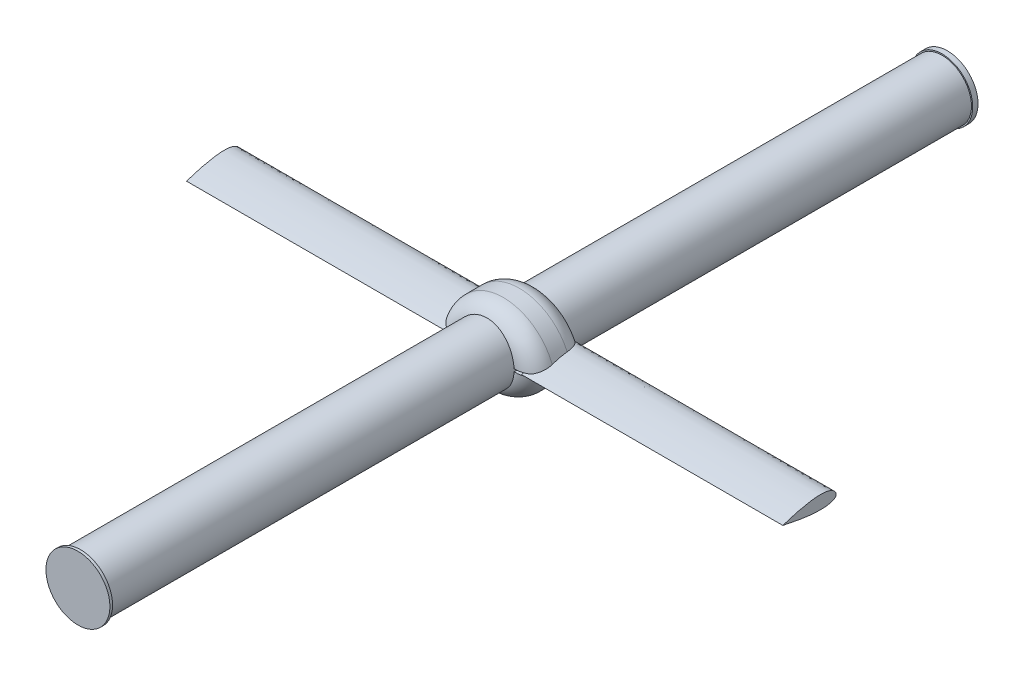
SolidWorks part; units mm, degrees
ref_plane "Front Plane" through (0, 0, 0) normal (0, 0, 1) x (1, 0, 0)
ref_plane "Top Plane" through (0, 0, 0) normal (0, 1, 0) x (1, 0, 0)
ref_plane "Right Plane" through (0, 0, 0) normal (1, 0, 0) x (0, 0, -1)
ref_plane "Plane1" through (0, 0, 10) normal (0, 0, 1) x (1, 0, 0)
sketch "Sketch1" plane through (0, 0, 10) normal (0, 0, 1) x (1, 0, 0)
  circle A0 centre (0, 0) radius 55.2
  dimension "D1" = 110.4
extrude "Boss-Extrude1" add sketch "Sketch1" along normal blind 798
sketch "Sketch3" plane through (0, 0, 808) normal (0, 0, 1) x (1, 0, 0)
  circle A0 centre (0, 0) radius 60
  dimension "D1" = 120
extrude "Boss-Extrude2" add sketch "Sketch3" along normal blind 5 contours A0
sketch "Sketch4" plane through (0, 0, 10) normal (0, 0, -1) x (-1, 0, 0)
  circle A0 centre (0, 0) radius 55.2
  dimension "D1" = 110.4
extrude "Boss-Extrude3" add sketch "Sketch4" along normal blind 20
sketch "Sketch5" plane through (0, 0, -10) normal (0, 0, -1) x (-1, 0, 0)
  circle A0 centre (0, 0) radius 55.2
  dimension "D1" = 110.4
extrude "Boss-Extrude4" add sketch "Sketch5" along normal blind 798
sketch "Sketch6" plane through (0, 0, -808) normal (0, 0, -1) x (-1, 0, 0)
  circle A0 centre (0, 0) radius 57.5
  dimension "D1" = 115
extrude "Boss-Extrude5" add sketch "Sketch6" along normal blind 10
sketch "Sketch10" plane through (0, 0, 0) normal (0, 0, 1) x (1, 0, 0)
  line L0 (-94.2708, 2.5) -> (-55.1434, 2.5)
  line L1 (55.1434, 2.5) -> (94.2708, 2.5)
  arc A0 (94.2708, 2.5) -> (-94.2708, 2.5) centre (0, -25) ccw
  arc A1 (55.1434, 2.5) -> (-55.1434, 2.5) centre (0, 0) ccw
  point P2 (0, 55.2)
  point P3 (0, -25)
  point P8 (0, 73.2)
  dimension "D1" = 55.2
  dimension "D2" = 18
  dimension "D3" = 0
  dimension "D4" = 25
  dimension "D5" = 2.5
extrude "Boss-Extrude8" add sketch "Sketch10" along normal mid plane 100
fillet "Fillet1" radius 35 1 edges at (0, 73.2, 50) type face fillet first side face at (0, 33.35, 50) second side face at (0, 37.85, 0)
fillet "Fillet2" radius 35 1 edges at (0, 73.2, -50) type face fillet first side face at (0, 33.35, -50) second side face at (0, 37.85, -17.5)
mirror "Mirror2" about plane through (0, 0, 0) normal (0, 1, 0) of "Fillet1", "Fillet2", "Boss-Extrude8"
ref_plane "Plane2" through (-94.2708, 0, 0) normal (-1, 0, 0) x (0, 0, 1)
ref_plane "Plane3" through (-69.2708, 0, 0) normal (-1, 0, 0) x (0, 0, 1)
sketch "Sketch11" plane through (-69.2708, 0, 0) normal (-1, 0, 0) x (0, 0, 1)
  spline S0 degree 4 poles (-50, 0) (-49.9991, 0.3297) (-49.9705, 0.9275) (-49.8561, 1.7967) (-49.563, 2.9181) (-49.1451, 3.9907) (-48.5685, 5.0756) (-47.8077, 6.1773) (-46.7997, 7.33) (-45.5041, 8.5106) (-43.846, 9.7149) (-41.7259, 10.9292) (-39.043, 12.1146) (-35.8523, 13.1525) (-31.9595, 14.0363) (-26.8657, 14.7366) (-20.7643, 15.0274) (-14.662, 14.8248) (-8.8989, 14.3138) (-3.159, 13.5968) (1.6037, 12.8505) (6.3456, 11.9834) (11.0671, 11.0139) (14.8328, 10.183) (18.5865, 9.3015) (22.3294, 8.3726) (26.0598, 7.3994) (29.3157, 6.5093) (32.096, 5.721) (34.4127, 5.0444) (36.2537, 4.4957) (38.1107, 3.9294) (39.9289, 3.3646) (41.806, 2.7666) (43.571, 2.1956) (45.5202, 1.5463) (47.1384, 1.0009) (49.1531, 0.3002) (50.3626, -0.127) (51.915, -0.6848) (53.1337, -1.1307) (54.3912, -1.5976) (55.6393, -2.0687) (56.8855, -2.5467) (58.1291, -3.0316) (59.0597, -3.4006) (59.6792, -3.6489) (59.9887, -3.7737) knots 0 0 0 0 0 0.011046 0.020082 0.029326 0.038802 0.04958 0.06121 0.074146 0.090071 0.108265 0.129827 0.155965 0.188307 0.220649 0.263591 0.328276 0.39296 0.425303 0.457645 0.522329 0.554672 0.587014 0.619356 0.651699 0.684041 0.716383 0.748725 0.764896 0.781068 0.797239 0.81341 0.829581 0.845752 0.861923 0.878094 0.894265 0.910437 0.921632 0.932827 0.944023 0.955218 0.966414 0.977609 0.988805 1 1 1 1 1 construction
  spline S1 degree 4 poles (-50, 0) (-49.9991, 0.3297) (-49.9705, 0.9275) (-49.8561, 1.7967) (-49.563, 2.9181) (-49.1451, 3.9907) (-48.5685, 5.0756) (-47.8077, 6.1773) (-46.7997, 7.33) (-45.5041, 8.5106) (-43.846, 9.7149) (-41.7259, 10.9292) (-39.043, 12.1146) (-35.8523, 13.1525) (-31.9595, 14.0363) (-26.8657, 14.7366) (-20.7643, 15.0274) (-14.662, 14.8248) (-8.8989, 14.3138) (-3.159, 13.5968) (1.6037, 12.8505) (6.3456, 11.9834) (11.0671, 11.0139) (14.8328, 10.183) (18.5865, 9.3015) (22.3294, 8.3726) (26.0598, 7.3994) (29.3157, 6.5093) (32.096, 5.721) (34.4127, 5.0444) (36.2537, 4.4957) (38.1107, 3.9294) (39.9289, 3.3646) (41.806, 2.7666) (43.571, 2.1956) (45.5202, 1.5463) (47.1383, 1.0009) (48.7751, 0.4317) (49.5867, 0.1465) (50.0002, 0) knots 0 0 0 0 0 0.011046 0.020082 0.029326 0.038802 0.04958 0.06121 0.074146 0.090071 0.108265 0.129827 0.155965 0.188307 0.220649 0.263591 0.328276 0.39296 0.425303 0.457645 0.522329 0.554672 0.587014 0.619356 0.651699 0.684041 0.716383 0.748725 0.764896 0.781068 0.797239 0.81341 0.829581 0.845752 0.861923 0.878094 0.894265 0.910434 0.910434 0.910434 0.910434 0.910434
  spline S2 degree 4 poles (-50, 0) (-49.9997, -0.1693) (-49.984, -0.4614) (-49.9225, -0.8851) (-49.7667, -1.4356) (-49.5488, -1.9609) (-49.237, -2.5157) (-48.8032, -3.1118) (-48.1991, -3.7667) (-47.3541, -4.4954) (-46.155, -5.3152) (-44.4798, -6.2106) (-42.1095, -7.1807) (-39.0529, -8.0963) (-34.5704, -9.0396) (-28.792, -9.73) (-22.0225, -10.0275) (-14.3514, -9.8891) (-7.6531, -9.4657) (-1.9252, -8.9399) (3.7915, -8.3061) (9.4968, -7.5766) (15.1885, -6.7461) (20.8667, -5.8302) (25.5899, -5.0142) (29.3624, -4.3307) (32.6596, -3.7058) (35.4801, -3.1515) (37.5962, -2.7233) (39.0005, -2.4341) (40.1811, -2.1872) (41.104, -1.9926) (42.3051, -1.7354) (43.6554, -1.4439) (45.3898, -1.0596) (47.1027, -0.6748) (49.4365, -0.1347) (51.1191, 0.2637) (53.9947, 0.9599) (55.7889, 1.4169) (57.9207, 1.9617) (59.0082, 2.2534) (59.6995, 2.4359) (59.9984, 2.5166) knots 0 0 0 0 0 0.005887 0.010193 0.014867 0.019889 0.025655 0.032315 0.040498 0.050865 0.064448 0.082823 0.106556 0.139954 0.175459 0.242256 0.309053 0.375849 0.442646 0.476045 0.509443 0.57624 0.643037 0.676435 0.709833 0.743232 0.77663 0.793329 0.810028 0.818378 0.826728 0.835077 0.843427 0.860126 0.876825 0.893524 0.910224 0.932668 0.955112 0.977556 0.988778 1 1 1 1 1 construction
  spline S3 degree 4 poles (-50, 0) (-49.9997, -0.1693) (-49.984, -0.4614) (-49.9225, -0.8851) (-49.7667, -1.4356) (-49.5488, -1.9609) (-49.237, -2.5157) (-48.8032, -3.1118) (-48.1991, -3.7667) (-47.3541, -4.4954) (-46.155, -5.3152) (-44.4798, -6.2106) (-42.1095, -7.1807) (-39.0529, -8.0963) (-34.5704, -9.0396) (-28.792, -9.73) (-22.0225, -10.0275) (-14.3514, -9.8891) (-7.6531, -9.4657) (-1.9252, -8.9399) (3.7915, -8.3061) (9.4968, -7.5766) (15.1885, -6.7461) (20.8667, -5.8302) (25.5899, -5.0142) (29.3624, -4.3307) (32.6596, -3.7058) (35.4801, -3.1515) (37.5962, -2.7233) (39.0005, -2.4341) (40.1811, -2.1872) (41.104, -1.9926) (42.3051, -1.7354) (43.6554, -1.4439) (45.3898, -1.0596) (47.1027, -0.6748) (48.7145, -0.3018) (49.5756, -0.1002) (50.0002, 0) knots 0 0 0 0 0 0.005887 0.010193 0.014867 0.019889 0.025655 0.032315 0.040498 0.050865 0.064448 0.082823 0.106556 0.139954 0.175459 0.242256 0.309053 0.375849 0.442646 0.476045 0.509443 0.57624 0.643037 0.676435 0.709833 0.743232 0.77663 0.793329 0.810028 0.818378 0.826728 0.835077 0.843427 0.860126 0.876825 0.893524 0.910224 0.910224 0.910224 0.910224 0.910224
  dimension "D1" = 50
extrude "Boss-Extrude9" add sketch "Sketch11" along normal blind 490
mirror "Mirror3" about plane through (0, 0, 0) normal (1, 0, 0) of "Boss-Extrude9"
